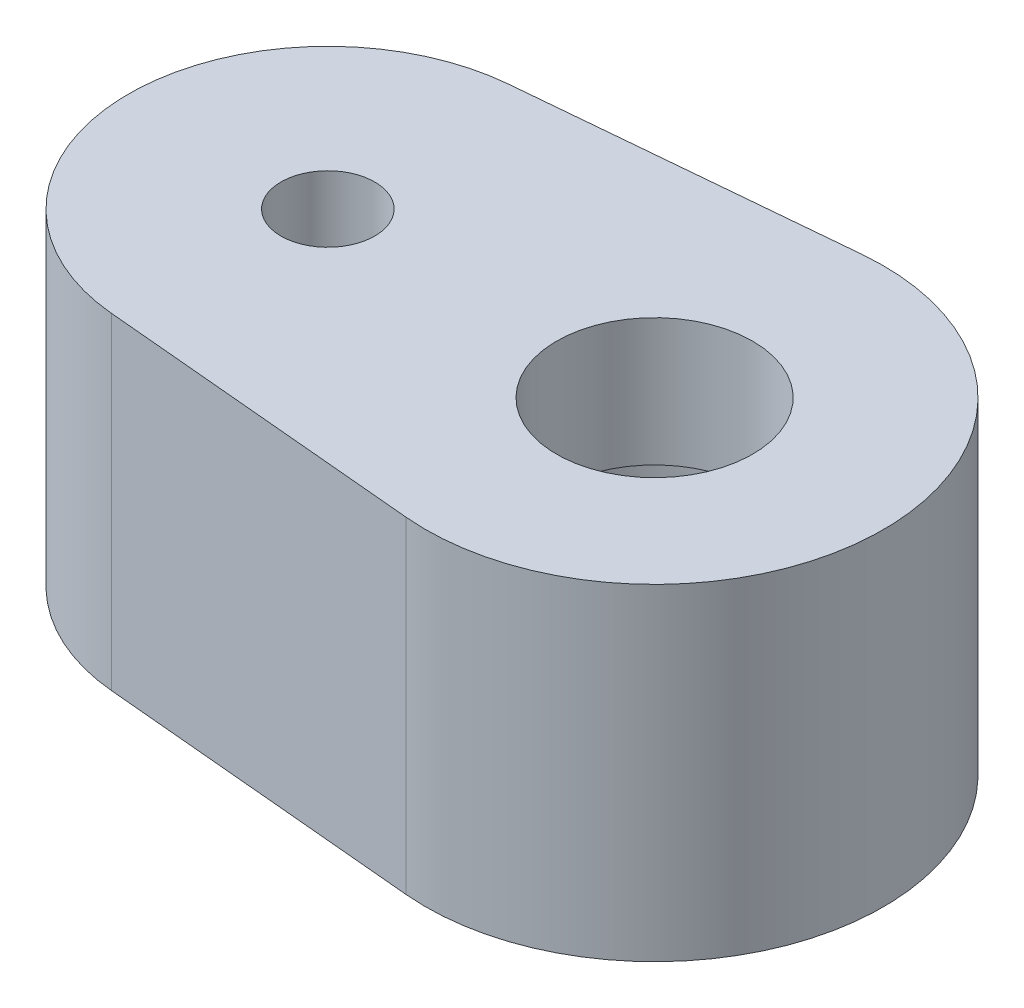
SolidWorks part; units mm, degrees
ref_plane "Front Plane" through (0, 0, 0) normal (0, 0, 1) x (1, 0, 0)
ref_plane "Top Plane" through (0, 0, 0) normal (0, 1, 0) x (1, 0, 0)
ref_plane "Right Plane" through (0, 0, 0) normal (1, 0, 0) x (0, 0, -1)
sketch "Sketch1" plane through (0, 0, 0) normal (0, 1, 0) x (1, 0, 0)
  line L0 (-2.1098, 1.215) -> (-0.126, 1.3943)
  line L1 (-2.1098, -1.215) -> (-0.126, -1.3943)
  line L2 (-2, 0) -> (0, 0) construction
  arc A0 (-0.126, -1.3943) -> (-0.126, 1.3943) centre (0, 0) ccw
  arc A1 (-2.1098, 1.215) -> (-2.1098, -1.215) centre (-2, 0) ccw
  dimension "D1" = 2.44
  dimension "D2" = 2.8
  dimension "D3" = 2
extrude "Boss-Extrude1" add sketch "Sketch1" along normal blind 1 and the other way blind 1
sketch "Sketch4" plane through (0, 0, 0) normal (0, 0, 1) x (1, 0, 0)
  line L0 (0.85, 0) -> (0.85, 0.075)
  line L1 (0.85, 0.075) -> (0.6, 0.2193)
  line L2 (0.6, 0.2193) -> (0.6, 1)
  line L3 (1.4, 1) -> (-0.126, 1) construction
  line L4 (0, 0) -> (0.85, 0) construction
  line L5 (0.85, 0) -> (0.85, -0.075)
  line L6 (0.85, -0.075) -> (0.6, -0.2193)
  line L7 (-0.126, -1) -> (1.4, -1) construction
  line L9 (0, -1) -> (0, 1)
  line L10 (0, 1) -> (0.6, 1)
  line L11 (0.6, -0.2193) -> (0.6, -1)
  line L12 (0, -1) -> (0.6, -1)
  dimension "D1" = 0.075
  dimension "D2" = 120
  dimension "D3" = 0.25
  dimension "D4" = 0.6
revolve "Cut-Revolve1" cut sketch "Sketch4" angle 360 about L9
sketch "Sketch5" plane through (0, 1, 0) normal (0, 1, 0) x (1, 0, 0)
  circle A0 centre (-2, 0) radius 0.287
  dimension "D1" = 0.574
extrude "Cut-Extrude1" cut sketch "Sketch5" against normal up to next
